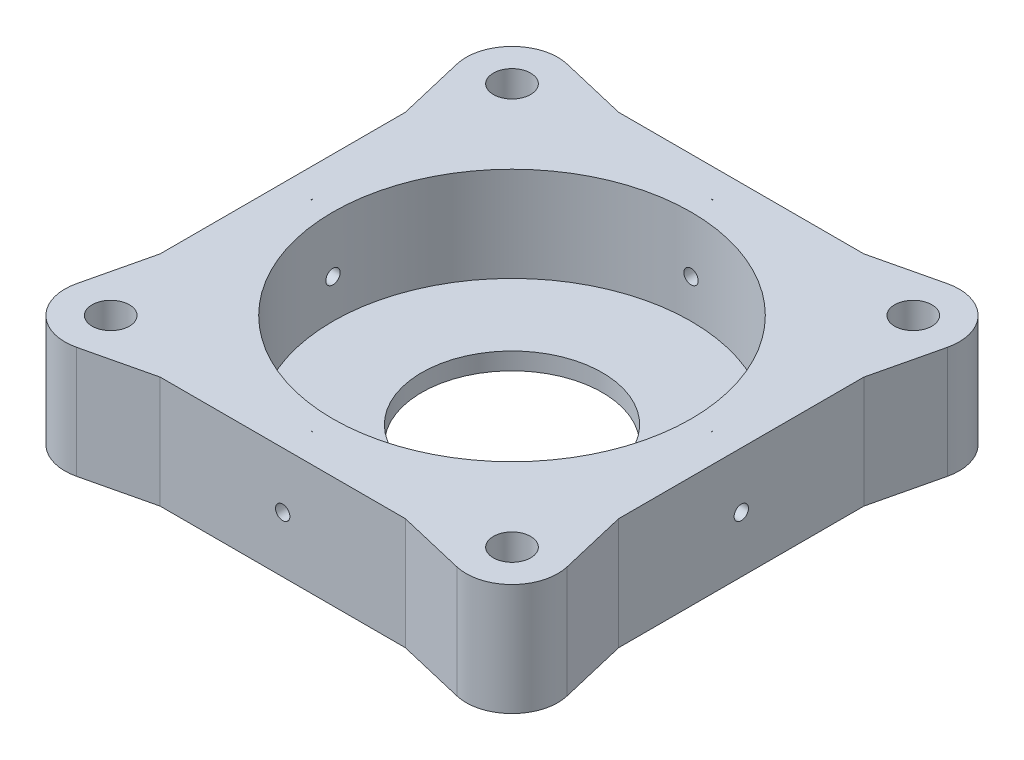
SolidWorks part; units mm, degrees
ref_plane "Front Plane" through (0, 0, 0) normal (0, 0, 1) x (1, 0, 0)
ref_plane "Top Plane" through (0, 0, 0) normal (0, 1, 0) x (1, 0, 0)
ref_plane "Right Plane" through (0, 0, 0) normal (1, 0, 0) x (0, 0, -1)
sketch "Sketch1" plane through (0, 0, 0) normal (0, 1, 0) x (1, 0, 0)
  line L0 (0, 35) -> (0, -35) construction
  line L1 (35, -35) -> (-35, -35)
  line L2 (35, -35) -> (35, 35)
  line L3 (35, 35) -> (-35, 35)
  line L4 (-35, -35) -> (-35, 35)
  line L5 (35, -35) -> (-35, 35) construction
  line L6 (35, 35) -> (-35, -35) construction
  line L7 (-35, 0) -> (35, 0) construction
  line L8 (-33.1578, 42.785) -> (7.8292, 33.0863)
  line L9 (-42.785, 33.1578) -> (-33.0863, -7.8292)
  line L10 (42.785, 33.1578) -> (33.0863, -7.8292)
  line L11 (33.1578, 42.785) -> (-7.8292, 33.0863)
  line L12 (-42.785, -33.1578) -> (-33.0863, 7.8292)
  line L13 (-33.1578, -42.785) -> (7.8292, -33.0863)
  line L14 (33.1578, -42.785) -> (-7.8292, -33.0863)
  line L15 (42.785, -33.1578) -> (33.0863, 7.8292)
  line L17 (40, -40) -> (-40, -40)
  line L18 (40, -40) -> (40, 40)
  line L19 (40, 40) -> (-40, 40)
  line L20 (-40, -40) -> (-40, 40)
  line L21 (40, -40) -> (-40, 40) construction
  line L22 (40, 40) -> (-40, -40) construction
  circle A0 centre (0, 0) radius 15.75
  circle A1 centre (0, 0) radius 34
  circle A2 centre (-35, 35) radius 3.25
  circle A3 centre (0, 0) radius 40
  circle A4 centre (-35, 35) radius 8
  circle A5 centre (35, 35) radius 3.25
  circle A6 centre (35, 35) radius 8
  circle A7 centre (-35, -35) radius 3.25
  circle A8 centre (-35, -35) radius 8
  circle A9 centre (35, -35) radius 3.25
  circle A10 centre (35, -35) radius 8
  dimension "D1" = 31.5
  dimension "D2" = 68
  dimension "D3" = 6.5
  dimension "D5" = 80
  dimension "D4" = 16
  dimension "D6" = 70
extrude "Boss-Extrude1" add sketch "Sketch1" along normal blind 19.5 contours L19 A4 L20 | L3 A4 L19 L20 L4 A2 | L4 A4 L3 A2 | A4 L9 L20 | A4 L20 L9 A3 L4 | A3 L9 L20 | L4 A3 L9 | L9 A3 L12 L4 | A3 L20 L12 | L12 A3 L4 | L20 A8 L4 A3 L12 | L12 A8 L20 | A8 L17 L20 | A8 L20 L17 L1 A7 L4 | A8 L4 A7 L1 | L4 A8 L1 A3 | L4 A3 L1 L13 L14 A1 L9 L12 | L3 A3 L4 L9 L12 A1 L11 L8 | A1 L12 L9 | A4 L4 A3 L3 | A4 L3 A3 L8 L19 | A4 L19 L8 | A3 L19 L8 | L8 A3 L3 | L11 A3 L8 L3 | A1 L8 L11 | L3 A3 L11 | L2 A3 L3 L11 L8 A1 L15 L10 | L3 A6 L19 L11 A3 | A3 L11 L19 | L19 A6 L11 | L2 A6 L3 A3 | A6 L2 A5 L3 | A6 L3 A5 L2 L18 L19 | A6 L19 L18 | L10 A6 L18 | L18 A6 L2 A3 L10 | A3 L18 L10 | L10 A3 L2 | L15 A3 L10 L2 | A3 L15 L18 | L2 A3 L15 | A1 L10 L15 | L1 A3 L2 L15 L10 A1 L13 L14 | A10 L18 L15 A3 L2 | A10 L15 L18 | A10 L2 A3 L1 | L18 A10 L2 A9 L1 L17 | L2 A10 L1 A9 | A10 L18 L17 | A10 L17 L14 | A10 L1 A3 L14 L17 | L14 A3 L1 | A3 L17 L14 | A3 L14 L1 L13 | A1 L14 L13 | L1 A3 L13 | A3 L13 L17 | L1 A8 L17 L13 A3 | L17 A8 L13 | A1 A0 region at (-27.625, 0, 37.5886) region at (-28.9419, 0, 28.9419) region at (-31.2062, 0, 31.2062) region at (-21.8672, 0, 37.555) region at (-24.6184, 0, 24.6184) region at (-10.9152, 0, 35.995) region at (-37.555, 0, 21.8672) region at (-30.8311, 0, 41.5907) region at (-27.2274, 0, 40.8217) region at (0, 0, 37.8149) region at (-35.995, 0, 10.9152) region at (-12.614, 0, 39.3478) region at (-40.8217, 0, 27.2274) region at (24.6184, 0, 24.6184) region at (10.9152, 0, 35.995) region at (0, 0, 34.191) region at (-37.8149, 0, 0) region at (-39.3478, 0, 12.614) region at (12.614, 0, 39.3478) region at (28.9419, 0, 28.9419) region at (21.8672, 0, 37.555) region at (0, 0, 33.0383) region at (-35.995, 0, -10.9152) region at (-24.6184, 0, -24.6184) region at (-34.191, 0, 0) region at (-39.3478, 0, -12.614) region at (27.2274, 0, 40.8217) region at (31.2062, 0, 31.2062) region at (29.375, 0, 35.1838) region at (37.555, 0, 21.8672) region at (35.995, 0, 10.9152) region at (34.191, 0, 0) region at (-37.555, 0, -21.8672) region at (-28.9419, 0, -28.9419) region at (-40.8217, 0, -27.2274) region at (30.8311, 0, 41.5907) region at (37.8149, 0, 0) region at (39.3478, 0, 12.614) region at (24.6184, 0, -24.6184) region at (-37.5886, 0, -27.625) region at (-31.2062, 0, -31.2062) region at (-10.9152, 0, -35.995) region at (-21.8672, 0, -37.555) region at (0, 0, -34.191) region at (-40.5144, 0, -40.5144) region at (40.8217, 0, 27.2274) region at (35.995, 0, -10.9152) region at (39.3478, 0, -12.614) region at (0, 0, -37.8149) region at (-12.614, 0, -39.3478) region at (-27.2274, 0, -40.8217) region at (28.9419, 0, -28.9419) region at (37.555, 0, -21.8672) region at (40.8217, 0, -27.2274) region at (10.9152, 0, -35.995) region at (12.614, 0, -39.3478) region at (31.2062, 0, -31.2062) region at (35.1838, 0, -29.375) region at (21.8672, 0, -37.555) region at (41.5907, 0, -30.8311)
sketch "Sketch2" plane through (0, 19.5, 0) normal (0, 1, 0) x (1, 0, 0)
  circle A0 centre (0, 0) radius 31.25
  dimension "D1" = 62.5
extrude "Cut-Extrude1" cut sketch "Sketch2" against normal blind 16.5
sketch "Sketch3" plane through (0, 0, 0) normal (0, -1, 0) x (1, 0, 0)
  circle A0 centre (-35, 35) radius 5.25
  circle A1 centre (35, 35) radius 5.25
  circle A2 centre (35, -35) radius 5.25
  circle A3 centre (-35, -35) radius 5.25
  dimension "D1" = 10.5
extrude "Cut-Extrude2" cut sketch "Sketch3" against normal blind 10
sketch "Sketch4" plane through (0, 0, 40) normal (0, 0, 1) x (1, 0, 0)
  line L0 (0, 0) -> (0, 19.5) construction
  line L1 (21.3883, 0) -> (-21.3883, 0) construction
  line L2 (21.3883, 19.5) -> (-21.3883, 19.5) construction
  circle A0 centre (0, 9.75) radius 1.25
  dimension "D1" = 2.5
extrude "Cut-Extrude3" cut sketch "Sketch4" against normal up to surface (80 mm away) up to face at (0, 9.75, -40)
sketch "Sketch5" plane through (40, 0, 0) normal (1, 0, 0) x (0, 0, -1)
  line L0 (0, 0) -> (0, 19.5) construction
  line L1 (-21.3883, 19.5) -> (21.3883, 19.5) construction
  circle A0 centre (0, 9.75) radius 1.25
  dimension "D1" = 2.5
extrude "Cut-Extrude4" cut sketch "Sketch5" against normal up to surface (80 mm away) up to face at (-40, 9.75, 0)
sketch "Sketch6" [suppressed] plane through (0, 19.5, 0) normal (0, 1, 0) x (1, 0, 0)
  line L12 (21.3883, -40) -> (33.1578, -42.785)
  line L13 (42.785, -33.1578) -> (40, -21.3883)
  line L14 (40, -21.3883) -> (40, 21.3883)
  line L15 (40, 21.3883) -> (42.785, 33.1578)
  line L16 (33.1578, 42.785) -> (21.3883, 40)
  line L17 (21.3883, 40) -> (-21.3883, 40)
  line L18 (-21.3883, 40) -> (-33.1578, 42.785)
  line L19 (-42.785, 33.1578) -> (-40, 21.3883)
  line L20 (-40, 21.3883) -> (-40, -21.3883)
  line L21 (-40, -21.3883) -> (-42.785, -33.1578)
  line L22 (-33.1578, -42.785) -> (-21.3883, -40)
  line L23 (-21.3883, -40) -> (21.3883, -40)
  line L24 (21.3883, -40) -> (33.1578, -42.785)
  line L25 (42.785, -33.1578) -> (40, -21.3883)
  line L26 (40, -21.3883) -> (40, 21.3883)
  line L27 (40, 21.3883) -> (42.785, 33.1578)
  line L28 (33.1578, 42.785) -> (21.3883, 40)
  line L29 (21.3883, 40) -> (-21.3883, 40)
  line L30 (-21.3883, 40) -> (-33.1578, 42.785)
  line L31 (-42.785, 33.1578) -> (-40, 21.3883)
  line L32 (-40, 21.3883) -> (-40, -21.3883)
  line L33 (-40, -21.3883) -> (-42.785, -33.1578)
  line L34 (-33.1578, -42.785) -> (-21.3883, -40)
  line L35 (-21.3883, -40) -> (21.3883, -40)
  circle A0 centre (0, 0) radius 31.25 construction
  circle A1 centre (35, 35) radius 3.25 construction
  circle A2 centre (-35, 35) radius 3.25 construction
  circle A3 centre (35, -35) radius 3.25 construction
  arc A4 (33.1578, -42.785) -> (42.785, -33.1578) centre (35, -35) ccw
  arc A5 (42.785, 33.1578) -> (33.1578, 42.785) centre (35, 35) ccw
  arc A6 (-33.1578, 42.785) -> (-42.785, 33.1578) centre (-35, 35) ccw
  arc A7 (-42.785, -33.1578) -> (-33.1578, -42.785) centre (-35, -35) ccw
  arc A8 (33.1578, -42.785) -> (42.785, -33.1578) centre (35, -35) ccw
  arc A9 (42.785, 33.1578) -> (33.1578, 42.785) centre (35, 35) ccw
  arc A10 (-33.1578, 42.785) -> (-42.785, 33.1578) centre (-35, 35) ccw
  arc A11 (-42.785, -33.1578) -> (-33.1578, -42.785) centre (-35, -35) ccw
  circle A12 centre (-35, -35) radius 3.25 construction
  circle A13 centre (0, 0) radius 31.25
  circle A14 centre (35, 35) radius 3.25
  circle A15 centre (-35, 35) radius 3.25
  circle A16 centre (35, -35) radius 3.25
  circle A17 centre (-35, -35) radius 3.25
  dimension "D1" = 0
extrude "Boss-Extrude4" [suppressed] add sketch "Sketch6" along normal blind 3.5
sketch "Sketch7" [suppressed] plane through (0, 0, 0) normal (0, -1, 0) x (1, 0, 0)
  line L0 (-35, 35) -> (-38.7123, 38.7123) construction
  line L1 (-29.1444, 33.431) -> (-30.7134, 39.2866)
  line L2 (-30.7134, 39.2866) -> (-36.569, 40.8556)
  line L3 (-36.569, 40.8556) -> (-40.8556, 36.569)
  line L4 (-40.8556, 36.569) -> (-39.2866, 30.7134)
  line L5 (-39.2866, 30.7134) -> (-33.431, 29.1444)
  line L6 (-33.431, 29.1444) -> (-29.1444, 33.431)
  line L7 (39.2866, 30.7134) -> (40.8556, 36.569)
  line L8 (40.8556, 36.569) -> (36.569, 40.8556)
  line L9 (36.569, 40.8556) -> (30.7134, 39.2866)
  line L10 (30.7134, 39.2866) -> (29.1444, 33.431)
  line L11 (29.1444, 33.431) -> (33.431, 29.1444)
  line L12 (33.431, 29.1444) -> (39.2866, 30.7134)
  line L13 (30.7134, -39.2866) -> (36.569, -40.8556)
  line L14 (36.569, -40.8556) -> (40.8556, -36.569)
  line L15 (40.8556, -36.569) -> (39.2866, -30.7134)
  line L16 (39.2866, -30.7134) -> (33.431, -29.1444)
  line L17 (33.431, -29.1444) -> (29.1444, -33.431)
  line L18 (29.1444, -33.431) -> (30.7134, -39.2866)
  line L19 (-39.2866, -30.7134) -> (-40.8556, -36.569)
  line L20 (-40.8556, -36.569) -> (-36.569, -40.8556)
  line L21 (-36.569, -40.8556) -> (-30.7134, -39.2866)
  line L22 (-30.7134, -39.2866) -> (-29.1444, -33.431)
  line L23 (-29.1444, -33.431) -> (-33.431, -29.1444)
  line L24 (-33.431, -29.1444) -> (-39.2866, -30.7134)
  line L25 (0, 40) -> (0, -40) construction
  line L26 (21.3883, 40) -> (-21.3883, 40) construction
  line L27 (21.3883, -40) -> (-21.3883, -40) construction
  circle A0 centre (-35, 35) radius 5.25 construction
  point P32 (0, 0)
  dimension "D1" = 10.5
  dimension "D2" = 4
extrude "Cut-Extrude5" [suppressed] cut sketch "Sketch7" against normal offset from surface (21.5 mm away) 1.5 up to face at (35, 0, 29.75)
